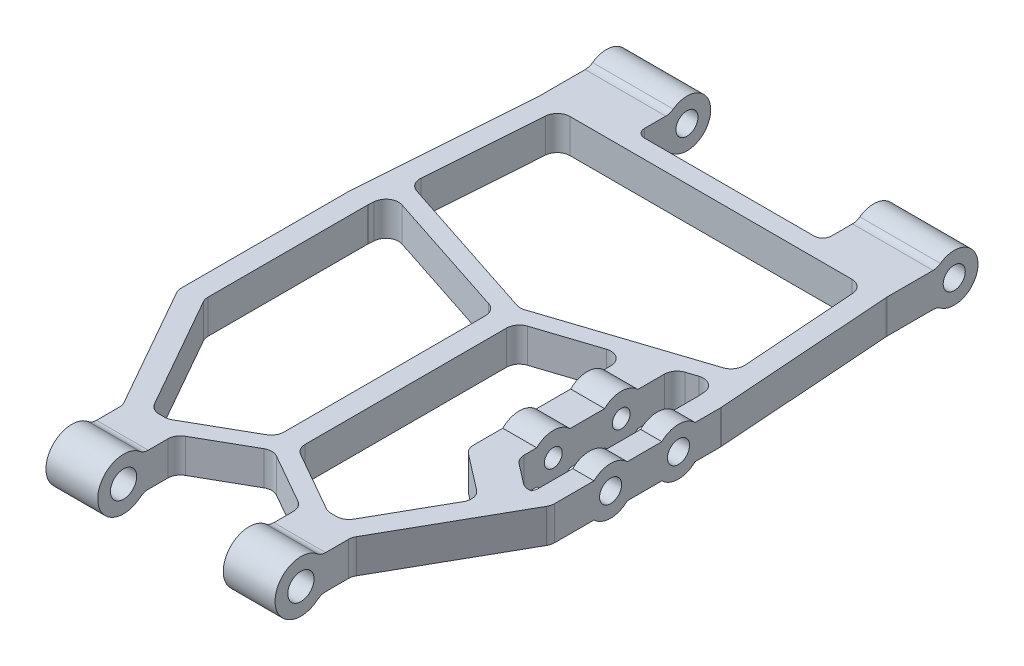
SolidWorks part; units mm, degrees
material "7050-T73510"
ref_plane "前视基准面" through (0, 0, 0) normal (0, 0, 1) x (1, 0, 0)
ref_plane "上视基准面" through (0, 0, 0) normal (0, 1, 0) x (1, 0, 0)
ref_plane "右视基准面" through (0, 0, 0) normal (1, 0, 0) x (0, 0, -1)
sketch "草图1" plane through (0, 0, 0) normal (0, 1, 0) x (1, 0, 0)
  line L0 (-41, 0) -> (41, 0) construction
  line L1 (0, 0) -> (0, -63.0258) construction
  line L2 (-27, -140) -> (27, -140) construction
  line L3 (-41, 4) -> (41, 4)
  line L4 (-24, -144) -> (24, -144)
  line L5 (41, 4) -> (41, 0)
  line L6 (-41, 4) -> (-41, 0)
  line L7 (41, 0) -> (41, -15.893)
  line L8 (41.0076, -16.1067) -> (43.9924, -57.8933)
  line L9 (44, -58.107) -> (44, -97.2091)
  line L10 (43.6101, -98.6881) -> (27.3899, -127.3119)
  line L11 (27, -128.7909) -> (27, -140)
  line L12 (-27, -128.7909) -> (-27, -140)
  line L13 (-43.6101, -98.6881) -> (-27.3899, -127.3119)
  line L14 (-44, -58.107) -> (-44, -97.2091)
  line L15 (-41.0076, -16.1067) -> (-43.9924, -57.8933)
  line L16 (-41, 0) -> (-41, -15.893)
  line L17 (-27, -140) -> (-27, -141)
  line L18 (27, -140) -> (27, -141)
  line L19 (36.2117, -19.1425) -> (38.9924, -58.0716)
  line L20 (39, -58.2854) -> (39, -95.8909)
  line L21 (38.6101, -97.3699) -> (23.5118, -124.014)
  line L22 (-36.2117, -19.1425) -> (-38.9924, -58.0716)
  line L23 (-39, -58.2854) -> (-39, -95.8909)
  line L24 (-38.6101, -97.3699) -> (-23.5118, -124.014)
  line L25 (-14.8, -144) -> (-14.8, -125.5349)
  line L26 (-14.8, -125.5349) -> (-20.9017, -125.5349)
  line L27 (20.9017, -125.5349) -> (14.8, -125.5349)
  line L28 (14.8, -125.5349) -> (14.8, -144)
  line L29 (-22, -12) -> (22, -12)
  line L30 (-22, -12) -> (-22, 4)
  line L31 (22, -12) -> (22, 4)
  line L32 (22, -12) -> (36.0127, -16.3562) construction
  line L33 (-36.0127, -16.3562) -> (-22, -12) construction
  line L34 (-33.2193, -16.3562) -> (33.2193, -16.3562)
  line L35 (-27, -144) -> (27, -144) construction
  line L36 (-44, -58) -> (-44, -98) construction
  line L37 (-41, -16) -> (-44, -58) construction
  line L38 (-36.0127, -16.3562) -> (-39, -58.1783) construction
  line L39 (-39, -58.1783) -> (-39, -96.6818) construction
  line L40 (41, -16) -> (44, -58) construction
  line L41 (36.0127, -16.3562) -> (39, -58.1783) construction
  line L42 (39, -58.1783) -> (39, -96.6818) construction
  line L43 (44, -58) -> (44, -98) construction
  line L44 (44, -98) -> (27, -128) construction
  line L45 (39, -96.6818) -> (22.6499, -125.5349) construction
  line L46 (-39, -96.6818) -> (-22.6499, -125.5349) construction
  line L47 (-44, -98) -> (-27, -128) construction
  line L48 (-27, -141) -> (-27, -144)
  line L49 (-27, -144) -> (-24, -144)
  line L50 (27, -141) -> (27, -144)
  line L51 (27, -144) -> (24, -144)
  arc A2 (-44, -58.107) -> (-43.9924, -57.8933) centre (-41, -58.107) cw
  arc A3 (-38.9924, -58.0716) -> (-39, -58.2854) centre (-36, -58.2854) ccw
  arc A4 (41, -15.893) -> (41.0076, -16.1067) centre (44, -15.893) ccw
  arc A5 (-41.0076, -16.1067) -> (-41, -15.893) centre (-44, -15.893) ccw
  arc A6 (38.9924, -58.0716) -> (39, -58.2854) centre (36, -58.2854) cw
  arc A7 (43.9924, -57.8933) -> (44, -58.107) centre (41, -58.107) cw
  arc A8 (44, -97.2091) -> (43.6101, -98.6881) centre (41, -97.2091) cw
  arc A9 (39, -95.8909) -> (38.6101, -97.3699) centre (36, -95.8909) cw
  arc A10 (-39, -95.8909) -> (-38.6101, -97.3699) centre (-36, -95.8909) ccw
  arc A11 (-43.6101, -98.6881) -> (-44, -97.2091) centre (-41, -97.2091) cw
  arc A12 (27.3899, -127.3119) -> (27, -128.7909) centre (30, -128.7909) ccw
  arc A13 (-27, -128.7909) -> (-27.3899, -127.3119) centre (-30, -128.7909) ccw
  arc A14 (-23.5118, -124.014) -> (-20.9017, -125.5349) centre (-20.9017, -122.5349) ccw
  arc A15 (23.5118, -124.014) -> (20.9017, -125.5349) centre (20.9017, -122.5349) cw
  arc A16 (36.2117, -19.1425) -> (33.2193, -16.3562) centre (33.2193, -19.3562) ccw
  arc A17 (-36.2117, -19.1425) -> (-33.2193, -16.3562) centre (-33.2193, -19.3562) cw
  point P4 (0, 0)
  point P10 (0, -140)
  point P37 (0, -12)
  point P48 (-44, -58)
  point P55 (41, -16)
  dimension "D1" = 82
  dimension "D2" = 54
  dimension "D3" = 140
  dimension "D7" = 44
  dimension "D9" = 16
  dimension "D13" = 12.2
  dimension "D14" = 12.2
  dimension "D15" = 16
  dimension "D16" = 19
  dimension "D4" = 4
  dimension "D5" = 4
  dimension "D11" = 5
  dimension "D12" = 5
extrude "凸台-拉伸1" add sketch "草图1" along normal mid plane 8 contours L22 A17 L34 A16 L19 A6 L20 A9 L21 A15 L27 L28 L4 L18 L11 A12 L10 A8 L9 A7 L8 A4 L7 L5 L3 L31 L29 L30 L6 L16 A5 L15 A2 L14 A11 L13 A13 L12 L17 L25 L26 A14 L24 A10 L23 A3 region at (-31.5, 0, -2.2781)
fillet "圆角1" radius 2 2 edges at (22, 0, 12) (-22, 0, 12)
fillet "圆角2" radius 4 4 edges at (-31.5, -4, -4) (-31.5, 4, -4) (31.5, -4, -4) (31.5, 4, -4)
sketch "草图2" plane through (41, 0, 0) normal (1, 0, 0) x (0, 0, -1)
  circle A0 centre (0, 0) radius 2.6
  dimension "D1" = 5.2
extrude "切除-拉伸1" cut sketch "草图2" against normal through all
sketch "草图3" plane through (0, 4, 0) normal (0, 1, 0) x (1, 0, 0)
  line L0 (0, 0) -> (0, -146.48) construction
  line L1 (40.7297, -50.2123) -> (0, -63.5538) construction
  line L2 (0, -63.5538) -> (0, -117.109) construction
  line L3 (0, -117.109) -> (14.8, -125.5349)
  line L4 (0, -117.109) -> (-14.8, -125.5349)
  line L5 (-40.7297, -50.2123) -> (0, -63.5538) construction
  line L6 (40.1071, -48.3116) -> (0, -61.4492)
  line L7 (-40.1071, -48.3116) -> (0, -61.4492)
  line L8 (2.5, -116.2309) -> (18.8424, -125.5349)
  line L9 (-2.5, -116.2309) -> (-18.8424, -125.5349)
  line L10 (41.3522, -52.1129) -> (2.5, -64.8394)
  line L11 (-41.3522, -52.1129) -> (-2.5, -64.8394)
  line L12 (0, -119.4104) -> (14.8, -127.8364)
  line L13 (0, -119.4104) -> (-14.8, -127.8364)
  line L14 (0, -119.4104) -> (13.8105, -127.273) construction
  line L15 (14.8, -125.5349) -> (14.8, -144) construction
  line L16 (20.9017, -125.5349) -> (14.8, -125.5349) construction
  line L17 (-14.8, -144) -> (-14.8, -125.5349) construction
  line L18 (-14.8, -125.5349) -> (-20.9017, -125.5349) construction
  line L19 (18.8424, -125.5349) -> (14.8, -125.5349)
  line L20 (14.8, -125.5349) -> (14.8, -127.8364)
  line L21 (-14.8, -127.8364) -> (-14.8, -125.5349)
  line L22 (-14.8, -125.5349) -> (-18.8424, -125.5349)
  line L23 (0, -114.8076) -> (-15.7895, -123.7969) construction
  line L24 (0, -119.4104) -> (-13.8105, -127.273) construction
  line L25 (0, -114.8076) -> (15.7895, -123.7969) construction
  line L26 (-2.5, -64.8394) -> (-2.5, -116.2309)
  line L27 (2.5, -64.8394) -> (2.5, -116.2309)
  line L28 (40.1071, -48.3116) -> (41.3522, -52.1129)
  line L29 (-40.1071, -48.3116) -> (-41.3522, -52.1129)
  line L30 (-2.5, -63.5538) -> (-2.5, -117.109) construction
  line L31 (2.5, -63.5538) -> (2.5, -117.109) construction
  line L32 (41.3522, -52.1129) -> (0, -65.6583) construction
  line L33 (-41.3522, -52.1129) -> (0, -65.6583) construction
  line M20 (-14.8, -144) -> (-14.8, -125.5349)
  line M21 (-14.8, -125.5349) -> (-20.9017, -125.5349)
  line M27 (-38.9924, -58.0716) -> (-36.2117, -19.1425)
  line M31 (36.2117, -19.1425) -> (38.9924, -58.0716)
  line M37 (20.9017, -125.5349) -> (14.8, -125.5349)
  line M38 (14.8, -125.5349) -> (14.8, -144)
  dimension "D1" = 2
  dimension "D2" = 2
  dimension "D3" = 2.5
  dimension "D4" = 2.5
extrude "凸台-拉伸3" add sketch "草图3" against normal up to surface (8 mm away) contours L27 L10 L6 L7 L11 L26 L9 L4 L3 L8 M31 M27 M21 M37 | L13 L12 L3 L4 M38 M20 region at (0, 4, 77.5401) region at (7.2442, 4, 121.5956) up to face at (0, -4, 70.8871)
sketch "草图4" plane through (0, 4, 0) normal (0, 1, 0) x (1, 0, 0)
  line L0 (26.5, -56.9779) -> (26.5, -94.314) construction
  line L1 (38.6304, -53.0045) -> (2.5, -64.8394) construction
  line L2 (26.5, -94.314) -> (36.1346, -101.7383) construction
  line L3 (38.6101, -97.3699) -> (23.5118, -124.014) construction
  line L4 (39, -58.2854) -> (39, -95.8909) construction
  line L5 (22.5, -58.2882) -> (22.5, -96.2814)
  line L6 (22.5, -96.2814) -> (34.1428, -105.2533)
  line L7 (30.5, -55.6677) -> (30.5, -92.3465)
  line L8 (30.5, -92.3465) -> (38.1264, -98.2234)
  line L9 (38.1264, -98.2234) -> (34.1428, -105.2533)
  line L10 (30.5, -55.6677) -> (22.5, -58.2882)
  line L11 (30.5, -56.9779) -> (30.5, -92.3465) construction
  line L12 (22.5, -96.2814) -> (33.6931, -104.9067) construction
  line L13 (22.5, -56.9779) -> (22.5, -96.2814) construction
  line L14 (30.5, -92.3465) -> (38.5762, -98.5699) construction
  dimension "D1" = 12.5
  dimension "D2" = 4
  dimension "D3" = 4
extrude "凸台-拉伸4" add sketch "草图4" against normal up to surface (8 mm away) up to face at (0, -4, 70.8359)
fillet "圆角3" radius 3 15 edges at (2.5, 0, 116.2309) (-2.5, 0, 116.2309) (-2.5, 0, 64.8394) (-38.6304, 0, 53.0045) (-38.3367, 0, 48.8916) (0, 0, 61.4492) (38.3367, 0, 48.8916) (38.6304, 0, 53.0045) (30.5, 0, 55.6677) (30.5, 0, 92.3465) (38.1264, 0, 98.2234) (34.1428, 0, 105.2533) (22.5, 0, 96.2814) (22.5, 0, 58.2882) (2.5, 0, 64.8394)
fillet "圆角4" radius 3 3 edges at (-14.8, 0, 127.8364) (14.8, 0, 127.8364) (0, 0, 119.4104)
fillet "圆角5" radius 3 2 edges at (18.8424, 0, 125.5349) (-18.8424, 0, 125.5349)
fillet "圆角6" radius 4 4 edges at (20.9, -4, 144) (-20.9, -4, 144) (-20.9, 4, 144) (20.9, 4, 144)
sketch "草图5" plane through (27, 0, 0) normal (1, 0, 0) x (0, 0, -1)
  circle A0 centre (-140, 0) radius 3.1
  dimension "D1" = 6.2
extrude "切除-拉伸2" cut sketch "草图5" against normal through all and the other way through all
sketch "草图6" plane through (27, 0, 0) normal (1, 0, 0) x (0, 0, -1)
  circle A1 centre (-140, 0) radius 3.1 construction
  circle A2 centre (-140, 0) radius 6.1
  circle A3 centre (-140, 0) radius 6.1
  circle A4 centre (-140, 0) radius 0.1
  circle A5 centre (-140, 0) radius 0.1
  circle A6 centre (-140, 0) radius 3.1
  arc M4 (-140, 4) -> (-144, 0) centre (-140, 0) ccw
  arc M5 (-144, 0) -> (-140, -4) centre (-140, 0) ccw
  line M6 (-140, -4) -> (-128.7909, -4)
  line M8 (-128.7909, 4) -> (-140, 4)
  dimension "D1" = 3
  dimension "D2" = 3
extrude "凸台-拉伸5" add sketch "草图6" against normal up to surface (12.2 mm away) contours A3 M8 M6 M5 M4 region at (27, 4.1623, 137.6973) up to face at (14.8, 0, 136.9)
sketch "草图7" plane through (-27, 0, 0) normal (-1, 0, 0) x (0, 0, 1)
  circle A1 centre (140, 0) radius 3.1
  circle A2 centre (140, 0) radius 3.1
  circle A3 centre (140, 0) radius 0.1
  circle A4 centre (140, 0) radius 0.1
  circle A5 centre (140, 0) radius 6.1
  circle A6 centre (140, 0) radius 6.1
  line M5 (128.7909, -4) -> (140, -4)
  arc M6 (140, -4) -> (144, 0) centre (140, 0) ccw
  arc M7 (144, 0) -> (140, 4) centre (140, 0) ccw
  line M8 (140, 4) -> (128.7909, 4)
  dimension "D1" = 0
  dimension "D2" = 0
  dimension "D3" = 0
extrude "凸台-拉伸6" add sketch "草图7" against normal up to surface (12.2 mm away) contours A6 M5 M8 M7 M6 region at (-27, -5.5621, 142.0782) up to face at (-14.8, 0, 143.1)
fillet "圆角7" radius 3 4 edges at (-20.9, -4, 135.3946) (20.9, -4, 135.3946) (20.9, 4, 135.3946) (-20.9, 4, 135.3946)
sketch "草图8" plane through (44, 0, 0) normal (1, 0, 0) x (0, 0, -1)
  circle A0 centre (-68, 0) radius 2.6
  circle A1 centre (-84, 0) radius 2.6
  dimension "D1" = 68
  dimension "D2" = 16
  dimension "D3" = 5.2
extrude "切除-拉伸3" cut sketch "草图8" against normal blind 8
sketch "草图9" plane through (30.5, 0, 0) normal (1, 0, 0) x (0, 0, -1)
  circle A0 centre (-68, 0) radius 2.6 construction
  circle A1 centre (-84, 0) radius 2.6 construction
  circle A2 centre (-68, 0) radius 2.6
  circle A3 centre (-84, 0) radius 2.6
  circle A4 centre (-68, 0) radius 5.6
  circle A5 centre (-84, 0) radius 5.6
  dimension "D1" = 3
extrude "凸台-拉伸7" add sketch "草图9" against normal up to surface (8 mm away) up to face at (22.5, 0, 78.6168)
sketch "草图10" plane through (44, 0, 0) normal (1, 0, 0) x (0, 0, -1)
  circle A0 centre (-68, 0) radius 2.6 construction
  circle A1 centre (-84, 0) radius 2.6 construction
  circle A2 centre (-68, 0) radius 2.6
  circle A3 centre (-84, 0) radius 2.6
  circle A4 centre (-84, 0) radius 5.6
  circle A5 centre (-68, 0) radius 5.6
  dimension "D1" = 3
extrude "凸台-拉伸8" add sketch "草图10" against normal up to surface (5 mm away) up to face at (39, 0, 65.4)
sketch "草图11" plane through (30.5, 0, 0) normal (1, 0, 0) x (0, 0, -1)
  circle A0 centre (-68, 0) radius 2.6 construction
  circle A1 centre (-84, 0) radius 2.6 construction
  circle A2 centre (-68, 0) radius 2.6 construction
  circle A3 centre (-84, 0) radius 2.6 construction
  circle A4 centre (-84, 0) radius 2
  circle A5 centre (-68, 0) radius 2
  dimension "D1" = 4
extrude "切除-拉伸4" cut sketch "草图11" against normal blind 8
hole_wizard "M5 螺纹孔2" positions "3D草图3" profile "草图14" tap size "M5" standard "GB"
sketch3d "3D草图3"
  line L0 (22.5, 0, 84) -> (30.5, 0, 84) construction
  line L1 (22.5, 0, 68) -> (30.5, 0, 68) construction
  point P0 (30.5, 0, 84)
  point P4 (30.5, 0, 68)
sketch "草图14" plane through (30.5, 0, 84) normal (0, 1, 0) x (0, 0, -1)
  line L0 (0, 0) -> (0, 13.6618)
  line L1 (0, 13.6618) -> (2.1, 12.4)
  line L2 (2.1, 12.4) -> (2.1, 0)
  line L5 (2.1, 0) -> (0, 0)
  line L10 (0, 13.6618) -> (-2.1, 12.4) construction
  line L11 (0, -6.35) -> (0, 107.95) construction
  dimension "螺纹孔钻头直径" = 4.2
  dimension "螺纹孔钻头深度" = 12.4
  dimension "导头角度" = 118
cosmetic thread "孔螺蚊线1" parameters "D1"=8, "D2"=5
cosmetic thread "孔螺蚊线2" parameters "D1"=8, "D2"=5
sketch "草图15" plane through (41, 0, 0) normal (1, 0, 0) x (0, 0, -1)
  circle A0 centre (0, 0) radius 2.6 construction
  circle A1 centre (0, 0) radius 2.6
  circle A2 centre (0, 0) radius 5.6
  dimension "D1" = 3
extrude "凸台-拉伸9" add sketch "草图15" against normal up to surface (19 mm away) up to face at (22, 0, 2.6)
sketch "草图16" plane through (-41, 0, 0) normal (-1, 0, 0) x (0, 0, 1)
  circle A1 centre (0, 0) radius 5.6
  circle A2 centre (0, 0) radius 5.6
  circle A3 centre (0, 0) radius 2.6
  circle A4 centre (0, 0) radius 2.6
  dimension "D1" = 0
  dimension "D2" = 0
extrude "凸台-拉伸10" add sketch "草图16" against normal up to surface (19 mm away) up to face at (-22, 0, 2.6)
fillet "圆角8" radius 3 4 edges at (-31.5, -4, 3.9192) (31.5, -4, 3.9192) (-31.5, 4, 3.9192) (31.5, 4, 3.9192)
